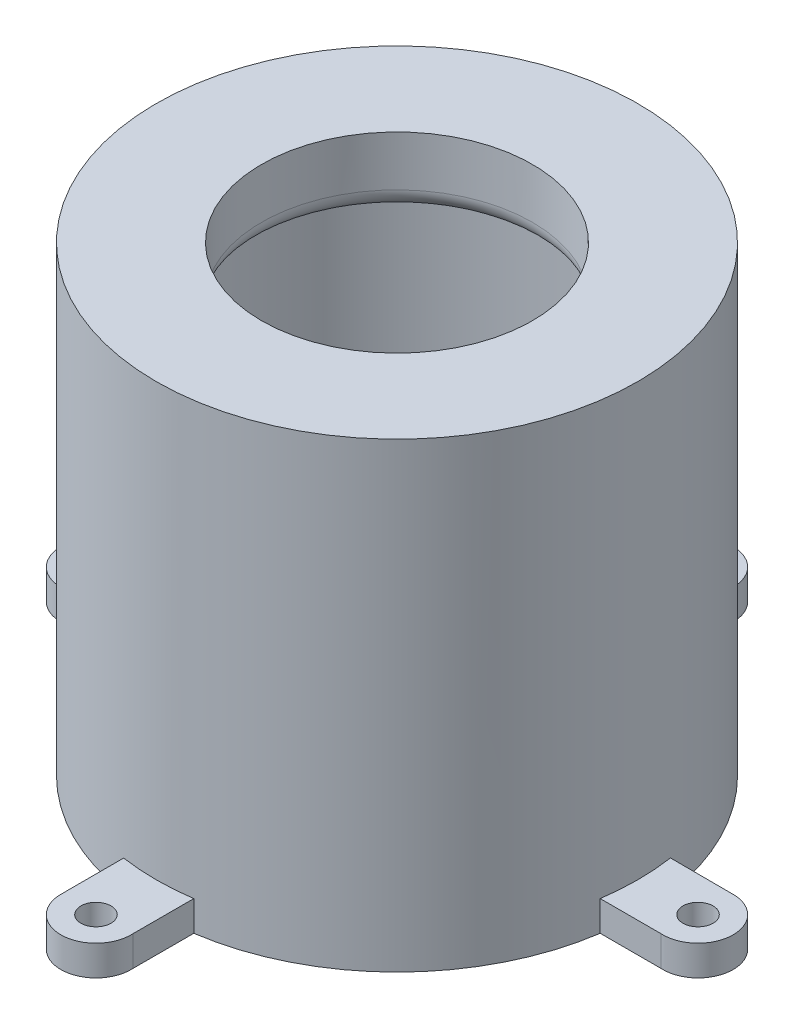
SolidWorks part; units mm, degrees
ref_plane "Front Plane" through (0, 0, 0) normal (0, 0, 1) x (1, 0, 0)
ref_plane "Top Plane" through (0, 0, 0) normal (0, 1, 0) x (1, 0, 0)
ref_plane "Right Plane" through (0, 0, 0) normal (1, 0, 0) x (0, 0, -1)
sketch "Sketch1" plane through (0, 0, 0) normal (0, 1, 0) x (1, 0, 0)
  line L0 (0, 0) -> (42.6804, 0) construction
  line L1 (0, 0) -> (0, 32.4742) construction
  line L2 (0, 0) -> (-30, 0) construction
  line L3 (0, 0) -> (0, 30) construction
  line L4 (-29.7958, -3.494) -> (-23.7443, -3.494)
  line L5 (-29.7743, 3.6734) -> (-23.72, 3.6552)
  line L6 (3.494, 23.7443) -> (3.494, 29.7958)
  line L7 (23.7443, -3.494) -> (29.7958, -3.494)
  line L8 (-3.5, -30) -> (-3.5, -23.7434)
  line L9 (-3.5, 29.7958) -> (-3.494, 29.7958)
  line L10 (3.494, -30) -> (3.494, -23.7443)
  line L12 (-3.5, 23.7434) -> (-3.5, 29.7958)
  line L13 (23.7416, 3.5123) -> (29.7958, 3.494)
  circle A0 centre (0, 0) radius 20
  circle A1 centre (30, 0) radius 1.5
  circle A2 centre (-30, 0) radius 1.5
  circle A3 centre (0, 30) radius 1.5
  circle A4 centre (0, -30) radius 1.5
  circle A5 centre (30, 0) radius 1.5
  circle A6 centre (-30, 0) radius 1.5
  circle A7 centre (0, -30) radius 1.5
  circle A8 centre (0, 30) radius 1.5
  circle A10 centre (30, 0) radius 3.5
  arc A11 (-3.494, -29.7958) -> (3.494, -29.7958) centre (0, -30) ccw
  circle A12 centre (0, 30) radius 3.5
  circle A13 centre (-30, 0) radius 3.5
  circle A14 centre (0, 0) radius 24
  arc A15 (3.494, 29.7958) -> (-3.5, 29.7951) centre (0, 0) ccw
  circle A16 centre (0, -30) radius 3.5 construction
  arc A17 (-29.7743, 3.6734) -> (-29.7958, -3.494) centre (0, 0) ccw
  arc A18 (-3.5, -29.7951) -> (-3.494, -29.7958) centre (0, 0) ccw
  point P43 (3.5, -30)
  dimension "D1" = 30
  dimension "D2" = 40
  dimension "D3" = 3
  dimension "D4" = 4
  dimension "D7" = 7
  dimension "D8" = 7
  dimension "D9" = 48
  dimension "D5" = 90
  dimension "D6" = 2
extrude "Boss-Extrude1" add sketch "Sketch1" along normal blind 3
sketch "Sketch2" plane through (0, 3, 0) normal (0, 1, 0) x (1, 0, 0)
  circle A0 centre (0, 0) radius 20
  circle A1 centre (0, 0) radius 24
extrude "Boss-Extrude2" add sketch "Sketch2" along normal blind 40
sketch "Sketch3" plane through (0, 43, 0) normal (0, 1, 0) x (1, 0, 0)
  circle A0 centre (0, 0) radius 24
extrude "Boss-Extrude3" add sketch "Sketch3" along normal blind 3
sketch "Sketch4" plane through (0, 46, 0) normal (0, 1, 0) x (1, 0, 0)
  circle A0 centre (0, 0) radius 13.5
  dimension "D1" = 27
extrude "Cut-Extrude1" cut sketch "Sketch4" against normal through all
sketch "Sketch5" plane through (0, 43, 0) normal (0, -1, 0) x (1, 0, 0)
  circle A0 centre (0, 0) radius 13.5
  circle A1 centre (0, 0) radius 15.5
  dimension "D1" = 31
extrude "Boss-Extrude4" add sketch "Sketch5" along normal blind 4
fillet "Fillet1" radius 1 1 edges at (0, 43, 15.5)
fillet "Fillet2" radius 2 1 edges at (0, 39, -13.5)
